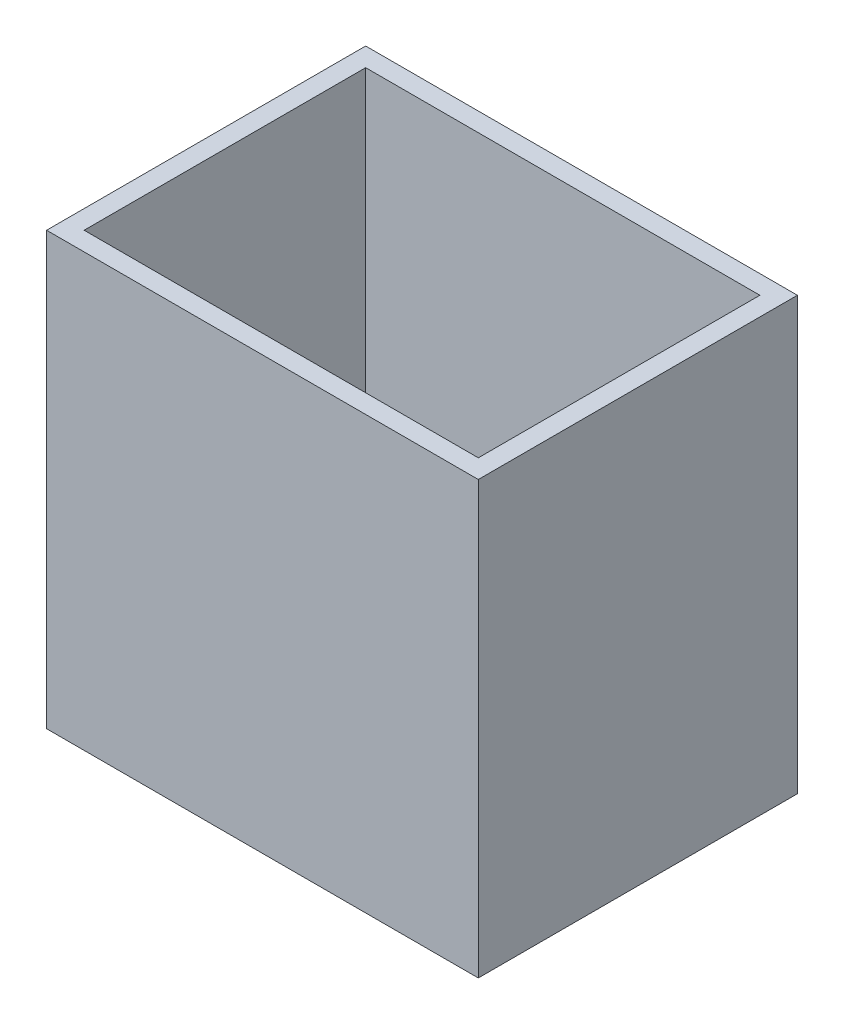
SolidWorks part; units mm, degrees
ref_plane "Front Plane" through (0, 0, 0) normal (0, 0, 1) x (1, 0, 0)
ref_plane "Top Plane" through (0, 0, 0) normal (0, 1, 0) x (1, 0, 0)
ref_plane "Right Plane" through (0, 0, 0) normal (1, 0, 0) x (0, 0, -1)
sketch "Sketch1" plane through (0, 0, 0) normal (0, 0, 1) x (1, 0, 0)
  line L1 (-23, 0) -> (23, 0)
  line L2 (-23, 0) -> (-23, 46)
  line L3 (-23, 46) -> (23, 46)
  line L4 (23, 0) -> (23, 46)
extrude "Boss-Extrude1" add sketch "Sketch1" along normal blind 34 from offset 17 offset against normal yes
sketch "Sketch2" plane through (0, 0, 0) normal (0, 0, 1) x (1, 0, 0)
  line L1 (-21, -1) -> (21, -1)
  line L2 (-21, -1) -> (-21, 47)
  line L3 (-21, 47) -> (21, 47)
  line L4 (21, -1) -> (21, 47)
extrude "Boss-Extrude2" add sketch "Sketch2" along normal blind 30 from offset 15 separate body offset against normal yes
combine bodies "Combine1" operation type subtract main body 101 bodies to subtract 102
